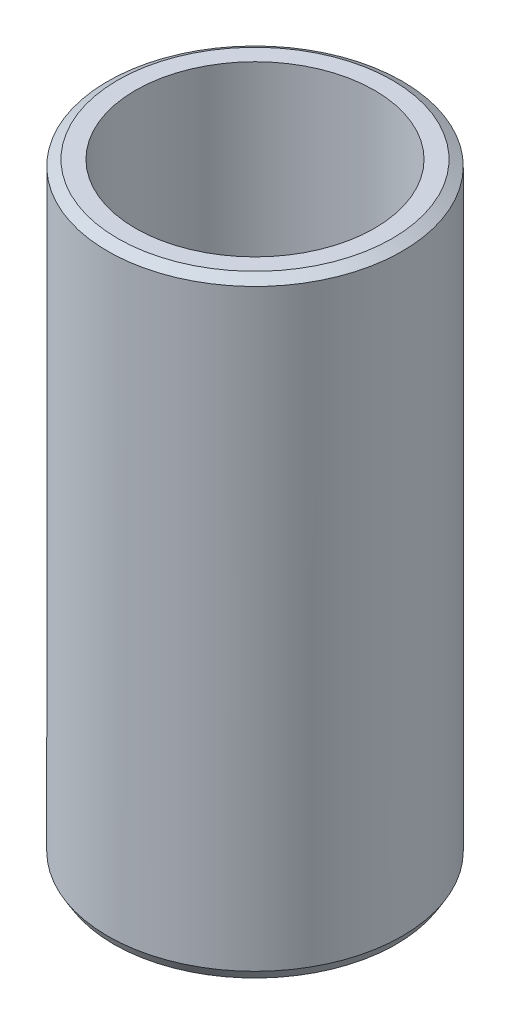
SolidWorks part; units mm, degrees
ref_plane "Front Plane" through (0, 0, 0) normal (0, 0, 1) x (1, 0, 0)
ref_plane "Top Plane" through (0, 0, 0) normal (0, 1, 0) x (1, 0, 0)
ref_plane "Right Plane" through (0, 0, 0) normal (1, 0, 0) x (0, 0, -1)
sketch "Sketch1" plane through (0, 0, 0) normal (0, 1, 0) x (1, 0, 0)
  circle A0 centre (0, 0) radius 47.5
  dimension "SHAFT_OD" = 95
extrude "Boss-Extrude1" add sketch "Sketch1" along normal blind 196.4857
sketch "Sketch2" plane through (0, 0, 0) normal (0, 1, 0) x (1, 0, 0)
  circle A0 centre (0, 0) radius 38.558
  dimension "BORE_D" = 77.1161
extrude "Cut-Extrude1" cut sketch "Sketch2" along normal through all
chamfer "Chamfer1" distance 1.937 angle 59.156 2 edges at (0, 196.4857, 47.5) (0, 0, 47.5) first distance on face at (0, 196.4857, 47.5) first distance on face at (0, 0, 38.558)
